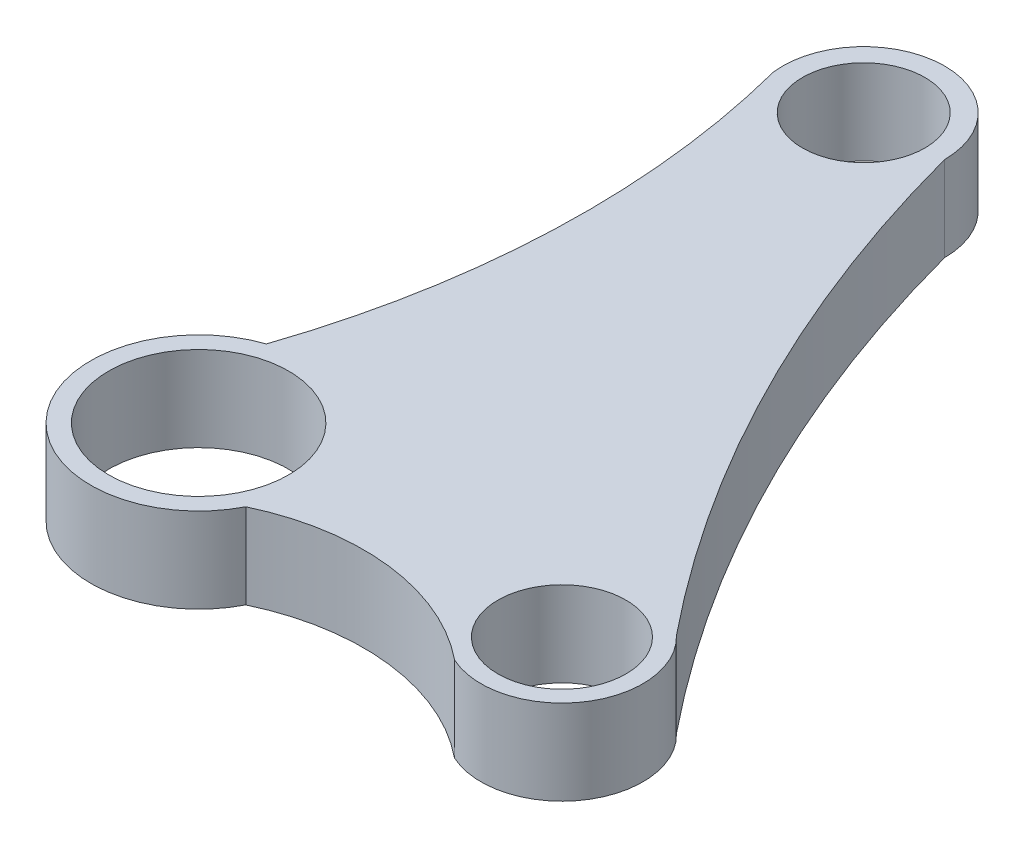
SolidWorks part; units mm, degrees
ref_plane "Front Plane" through (0, 0, 0) normal (0, 0, 1) x (1, 0, 0)
ref_plane "Top Plane" through (0, 0, 0) normal (0, 1, 0) x (1, 0, 0)
ref_plane "Right Plane" through (0, 0, 0) normal (1, 0, 0) x (0, 0, -1)
sketch "Sketch1" plane through (0, 0, 0) normal (0, 1, 0) x (1, 0, 0)
  circle A0 centre (0, 0) radius 12.7
  circle A1 centre (7.5123, 70.7221) radius 9.525
  circle A2 centre (43.1778, -0.4392) radius 9.525
  arc A3 (-1.9402, 69.5485) -> (-4.0643, 12.0321) centre (-99.381, 44.3497) cw
  arc A4 (17.0373, 70.7221) -> (49.7515, 6.4537) centre (184.3922, 115.4495) ccw
  arc A5 (11.3158, -5.7657) -> (39.2012, -9.0944) centre (22.6244, -29.496) cw
  circle A6 centre (7.5123, 70.7221) radius 7.1995
  circle A7 centre (0, 0) radius 10.5879
  circle A8 centre (43.1778, -0.4392) radius 7.5318
  point P19 (43.1036, 2.5677)
  point P20 (39.2012, -9.0944)
  point P21 (7.5123, 70.7221)
  point P22 (-4.0643, 12.0321)
  dimension "D1" = 19.05
  dimension "D2" = 25.4
  dimension "D3" = 19.05
  dimension "D5" = 43.18
  dimension ".8" = 71.12
extrude "Boss-Extrude1" add sketch "Sketch1" along normal blind 10 contours A0 A5 A2 A1 | A0 A7 | A1 A6 | A2 A8 region at (11.9998, 0, 2.8809) region at (18.0363, 0, -27.4999) region at (-1.4031, 0, -68.5226) region at (36.6053, 0, -6.0776)
ref_point "pivot pt"
ref_point "shock pt"
